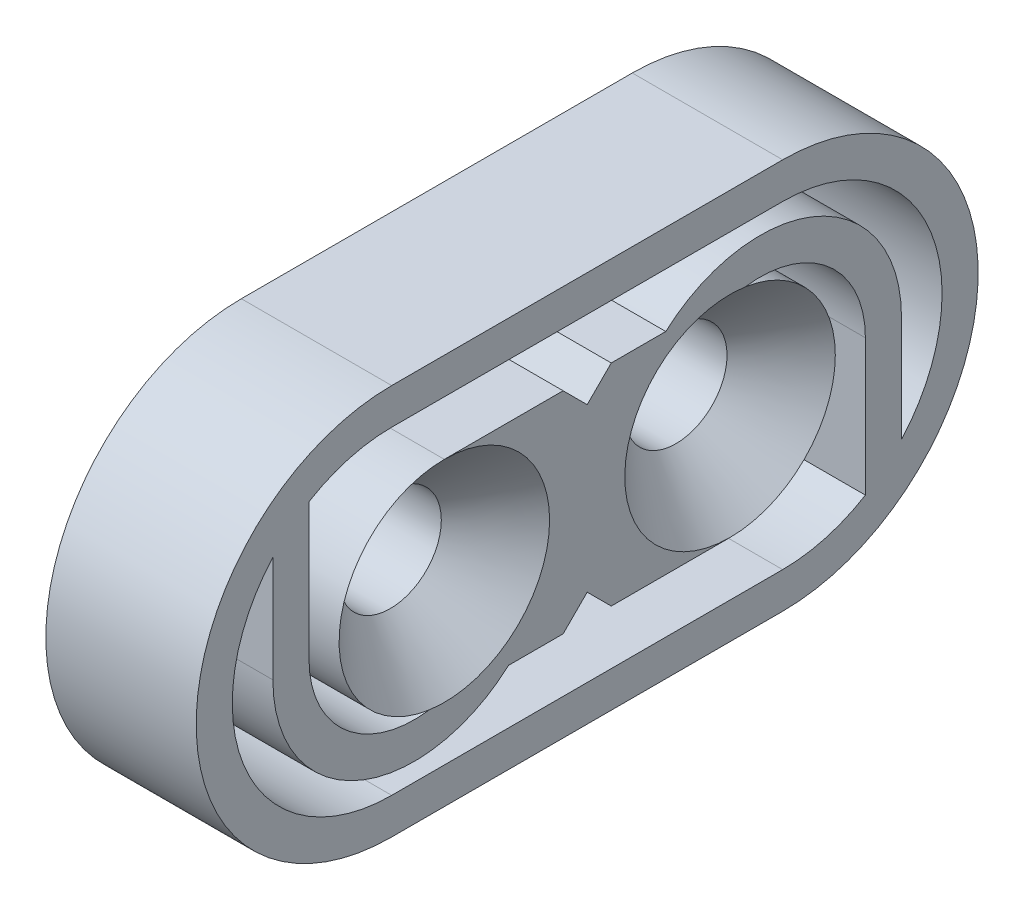
SolidWorks part; units mm, degrees
ref_plane "Front Plane" through (0, 0, 0) normal (1, 0, 0) x (0, 1, 0)
ref_plane "Top Plane" through (0, 0, 0) normal (0, 0, 1) x (0, 1, 0)
ref_plane "Right Plane" through (0, 0, 0) normal (0, 1, 0) x (-1, 0, 0)
sketch "Sketch2" plane through (0, 0, 0) normal (1, 0, 0) x (0, 1, 0)
  line L0 (-6.4721, 6.4962) -> (-6.4721, -6.5038)
  line L1 (-5.2721, 6.4962) -> (-5.2721, -6.5038)
  line L2 (0.0279, 10.4462) -> (3.5616, 10.4462)
  line L3 (4.5586, 9.2462) -> (0.0279, 9.2462)
  line L4 (-3.4721, 2.6094) -> (-3.4721, 0.7962)
  line L5 (-3.4721, 0.7962) -> (-2.6721, -0.0038)
  line L6 (-2.6721, -0.0038) -> (-3.4721, -0.8038)
  line L7 (-3.4721, -0.8038) -> (-3.4721, -4.7538)
  line L8 (3.5279, -2.6169) -> (3.5279, -0.8038)
  line L9 (3.5279, -0.8038) -> (2.7279, -0.0038)
  line L10 (2.7279, -0.0038) -> (3.5279, 0.7962)
  line L11 (3.5279, 0.7962) -> (3.5279, 4.7462)
  line L12 (5.3279, 6.4962) -> (5.3279, -6.5038)
  line L13 (6.5279, 6.4962) -> (6.5279, -6.5038)
  line L14 (-3.5059, -10.4538) -> (0.0279, -10.4538)
  line L15 (-4.5029, -9.2538) -> (0.0279, -9.2538)
  arc A0 (3.5279, 4.7462) -> (-3.4362, 5.2462) centre (0.0279, 4.7462) ccw
  arc A1 (0.0279, 10.4462) -> (-3.4721, 2.6094) centre (0.0279, 5.7462) ccw
  arc A2 (-6.4721, -6.5038) -> (6.5279, -6.5038) centre (0.0279, -6.5038) ccw
  arc A3 (-5.2721, -6.5038) -> (-4.5029, -9.2538) centre (0.0279, -6.5038) ccw
  arc A4 (5.3279, 6.4962) -> (4.5586, 9.2462) centre (0.0279, 6.4962) ccw
  arc A5 (6.5279, 6.4962) -> (-6.4721, 6.4962) centre (0.0279, 6.4962) ccw
  arc A6 (0.0279, -9.2538) -> (3.492, -5.2538) centre (0.0279, -5.7538) ccw
  arc A7 (0.0279, -10.4538) -> (3.5279, -2.6169) centre (0.0279, -5.7538) ccw
  arc A8 (-3.4721, -4.7538) -> (3.492, -5.2538) centre (0.0279, -4.7538) ccw
  arc A9 (0.0279, 9.2462) -> (-3.4362, 5.2462) centre (0.0279, 5.7462) ccw
  arc A10 (-3.5059, -10.4538) -> (5.3279, -6.5038) centre (0.0279, -6.5038) ccw
  arc A11 (3.5616, 10.4462) -> (-5.2721, 6.4962) centre (0.0279, 6.4962) ccw
  circle A12 centre (0.0279, 4.7462) radius 1.7
  circle A13 centre (0.0279, -4.7538) radius 1.7
extrude "Boss-Extrude2" add sketch "Sketch2" along normal blind 5
chamfer "Chamfer1" distance 1.8 angle 45 2 edges at (5, 0.0279, 3.0462) (5, 0.0279, -6.4538)
